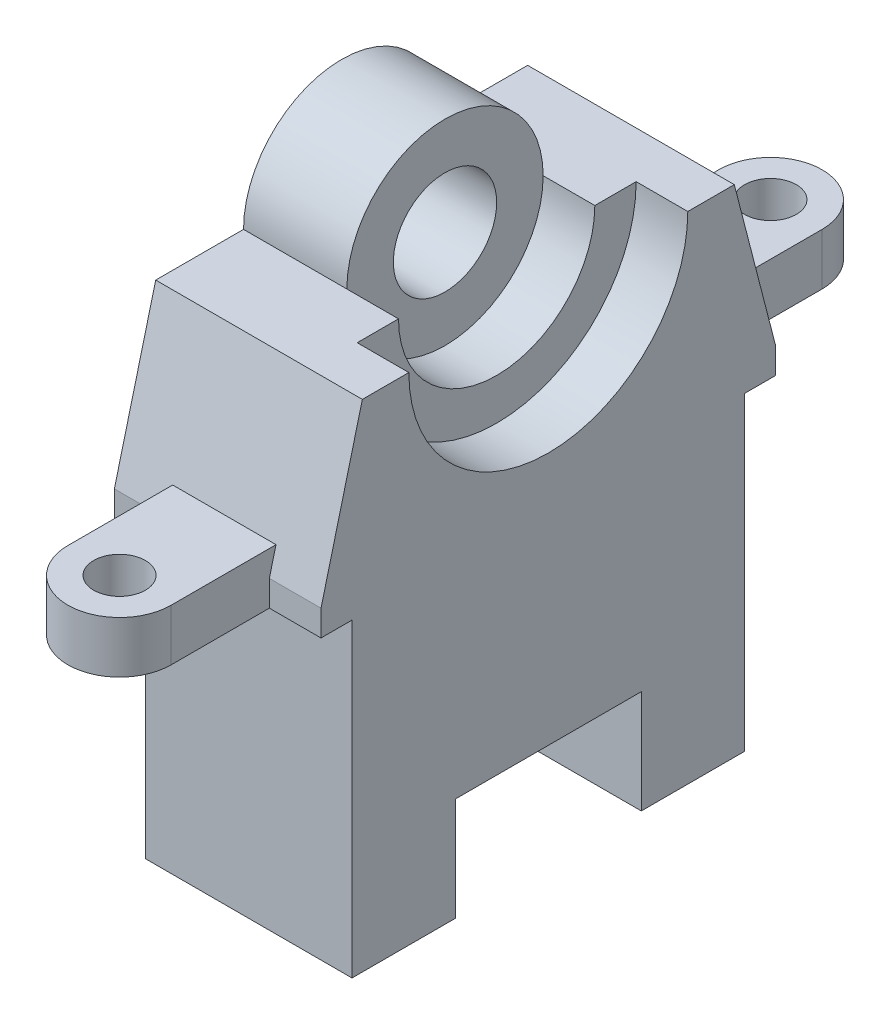
SolidWorks part; units mm, degrees
ref_plane "Front Plane" through (0, 0, 0) normal (0, 0, 1) x (1, 0, 0)
ref_plane "Top Plane" through (0, 0, 0) normal (0, 1, 0) x (1, 0, 0)
ref_plane "Right Plane" through (0, 0, 0) normal (1, 0, 0) x (0, 0, -1)
sketch "Sketch1" plane through (0, 0, 0) normal (1, 0, 0) x (0, 0, -1)
  line L0 (0, 0) -> (-21370.4259, 0) construction
  line L1 (0, 0) -> (0, -21370.4259) construction
  line L2 (27, 0) -> (36, 0)
  line L3 (36, 0) -> (44, -31)
  line L4 (44, -31) -> (44, -36)
  line L5 (44, -36) -> (38, -36)
  line L6 (38, -36) -> (38, -96)
  line L7 (38, -96) -> (18, -96)
  line L8 (18, -96) -> (18, -76)
  line L9 (18, -76) -> (-18, -76)
  line L10 (-18, -96) -> (-18, -76)
  line L11 (-38, -96) -> (-18, -96)
  line L12 (-38, -36) -> (-38, -96)
  line L13 (-44, -36) -> (-38, -36)
  line L14 (-44, -31) -> (-44, -36)
  line L15 (-36, 0) -> (-44, -31)
  line L16 (-27, 0) -> (-36, 0)
  line L17 (-27, 0) -> (-19, 0)
  line L18 (19, 0) -> (27, 0)
  circle A0 centre (0, 0) radius 10
  circle A1 centre (0, 0) radius 19
  arc A2 (-27, 0) -> (27, 0) centre (0, 0) ccw
  point P20 (0, -76)
  dimension "D1" = 20
  dimension "D2" = 38
  dimension "D3" = 54
  dimension "D4" = 36
  dimension "D5" = 88
  dimension "D6" = 72
  dimension "D7" = 5
  dimension "D8" = 76
  dimension "D9" = 36
  dimension "D10" = 20
  dimension "D11" = 60
extrude "Boss-Extrude1" add sketch "Sketch1" along normal blind 20 contours A1 A0 region at (0, -18.4626, 0)
extrude "Boss-Extrude2" add sketch "Sketch1<3>" along normal blind 30 contours L17 A2 L18 A1 region at (0, -26.3963, 0)
sketch "Sketch1<3>" plane through (0, 0, 0) normal (1, 0, 0) x (0, 0, -1) same geometry as "Sketch1"
extrude "Boss-Extrude3" add sketch "Sketch1<4>" along normal blind 40 contours A2 L16 L15 L14 L13 L12 L11 L10 L9 L8 L7 L6 L5 L4 L3 L2 region at (0, -49.935, 0)
sketch "Sketch1<4>" plane through (0, 0, 0) normal (1, 0, 0) x (0, 0, -1) same geometry as "Sketch1"
sketch "Sketch2" plane through (0, -36, 0) normal (0, -1, 0) x (1, 0, 0)
  line L0 (40, -38) -> (0, -38) construction
  line L1 (40, -44) -> (0, -44) construction
  line L2 (0, 0) -> (-50000, 0) construction
  line L3 (0, -18) -> (0, 18) construction
  line L10 (10, -63) -> (10, -42)
  line L11 (10, -42) -> (30, -42)
  line L12 (30, -42) -> (30, -63)
  line L13 (30, 42) -> (30, 63)
  line L14 (10, 42) -> (30, 42)
  line L15 (10, 63) -> (10, 42)
  circle A0 centre (20, -63) radius 5
  arc A1 (10, -63) -> (30, -63) centre (20, -63) ccw
  arc A4 (10, 63) -> (30, 63) centre (20, 63) cw
  circle A5 centre (20, 63) radius 5
  point P7 (20, -44)
  point P12 (0, 0)
  dimension "D1" = 20
  dimension "D2" = 10
  dimension "D3" = 25
  dimension "D4" = 2
extrude "Boss-Extrude4" add sketch "Sketch2" against normal blind 10
